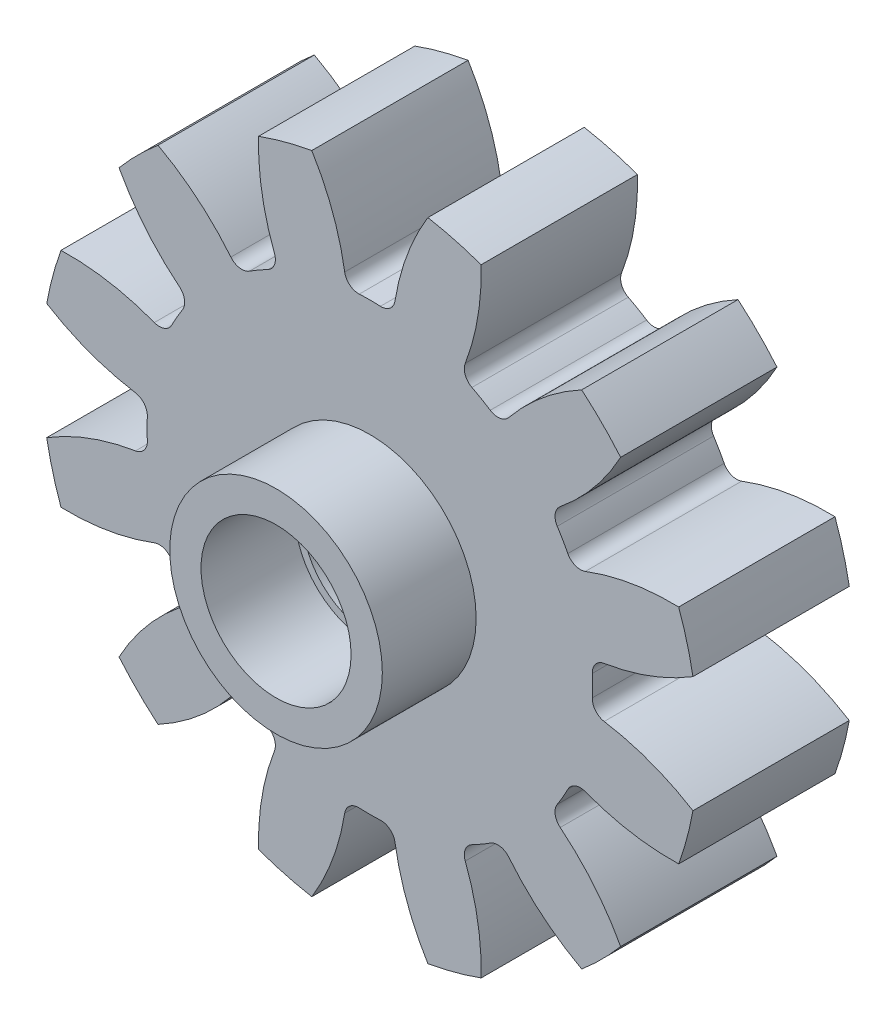
SolidWorks part; units mm, degrees
ref_plane "Front Plane" through (0, 0, 0) normal (0, 0, 1) x (1, 0, 0)
ref_plane "Top Plane" through (0, 0, 0) normal (0, 1, 0) x (1, 0, 0)
ref_plane "Right Plane" through (0, 0, 0) normal (1, 0, 0) x (0, 0, -1)
sketch "Sketch1" plane through (0, 0, 0) normal (0, 0, 1) x (1, 0, 0)
  circle A0 centre (0, 0) radius 9
  circle A1 centre (0, 0) radius 10.5
  circle A2 centre (0, 0) radius 7.125
  dimension "D1" = 18
  dimension "D2" = 21
  dimension "D4" = 3.375
extrude "Boss-Extrude1" add sketch "Sketch1" along normal mid plane 5 contours A1
sketch "Sketch2" plane through (0, 0, 0) normal (0, 0, 1) x (1, 0, 0)
  line L0 (0, 0) -> (0, 10.5) construction
  line L1 (-1.1747, 8.923) -> (1.1747, 8.923) construction
  line L2 (-0.7498, 7.0854) -> (0, 0) construction
  line L3 (-2.0459, 11.3165) -> (0, 5.6954) construction
  line L4 (0, 0) -> (2.7176, 10.1422) construction
  line L5 (1.1747, 8.923) -> (3.4442, 8.3149) construction
  circle A0 centre (0, 0) radius 10.5 construction
  arc A1 (-2.4962, 11.2258) -> (-0.7498, 7.0854) centre (-8.4673, 6.2687) cw
  arc A2 (2.4962, 11.2258) -> (0.7498, 7.0854) centre (8.4673, 6.2687) ccw
  circle A3 centre (0, 0) radius 7.125 construction
  circle A4 centre (0, 0) radius 10.5 construction
  arc A5 (0.7498, 7.0854) -> (-0.7498, 7.0854) centre (0, 0) ccw
  circle A6 centre (0, 0) radius 11.5
  arc A7 (2.4962, 11.2258) -> (-2.4962, 11.2258) centre (0, 0) ccw
  circle A8 centre (0, 0) radius 9 construction
  dimension "D2" = 20
  dimension "D3" = 15
extrude "Cut-Extrude1" cut sketch "Sketch2" against normal through all both and the other way through all
fillet "Fillet1" radius 0.45 2 edges at (0.7498, 7.0854, 0) (-0.7498, 7.0854, 0)
pattern_circular "CirPattern1" count 12 over 360 about axis through (0, 0, 2.5) along (0, 0, -1) of "Fillet1", "Cut-Extrude1"
sketch "Sketch3" plane through (0, 0, 2.5) normal (0, 0, 1) x (1, 0, 0)
  circle A0 centre (0, 0) radius 3.4
  circle A1 centre (0, 0) radius 2.4
  dimension "D1" = 6.8
  dimension "D2" = 4.8
extrude "Boss-Extrude2" add sketch "Sketch3" along normal blind 3
sketch "Sketch7" plane through (0, 0, 2.5) normal (0, 0, 1) x (1, 0, 0)
  circle A0 centre (0.8364, -2.2154) radius 0.218
  circle A1 centre (-0.3317, 2.0913) radius 0.0326
sketch "Sketch8" plane through (0, 0, 2.5) normal (0, 0, 1) x (1, 0, 0)
  circle A0 centre (0.0061, 0.0096) radius 2.1613
extrude "Cut-Extrude5" cut sketch "Sketch8" against normal blind 1
equation "\"module\"= 1.5mm"
equation "\"No. of teeth\" = 12"
equation "\"D1@Sketch1\"=\"module\"*\"No. of teeth\""
equation "\"D2@Sketch1\"=(\"No. of teeth\" + 2)* \"module\""
equation "\"D4@Sketch1\" = \"module\" * IIF ( \"module\" = > 1.25 , 2.25 , 2.4 )"
equation "\"D3@Sketch2\"=180 /  \"No. of teeth\""
equation "\"D1@Fillet1\"= .3 * \"module\""
